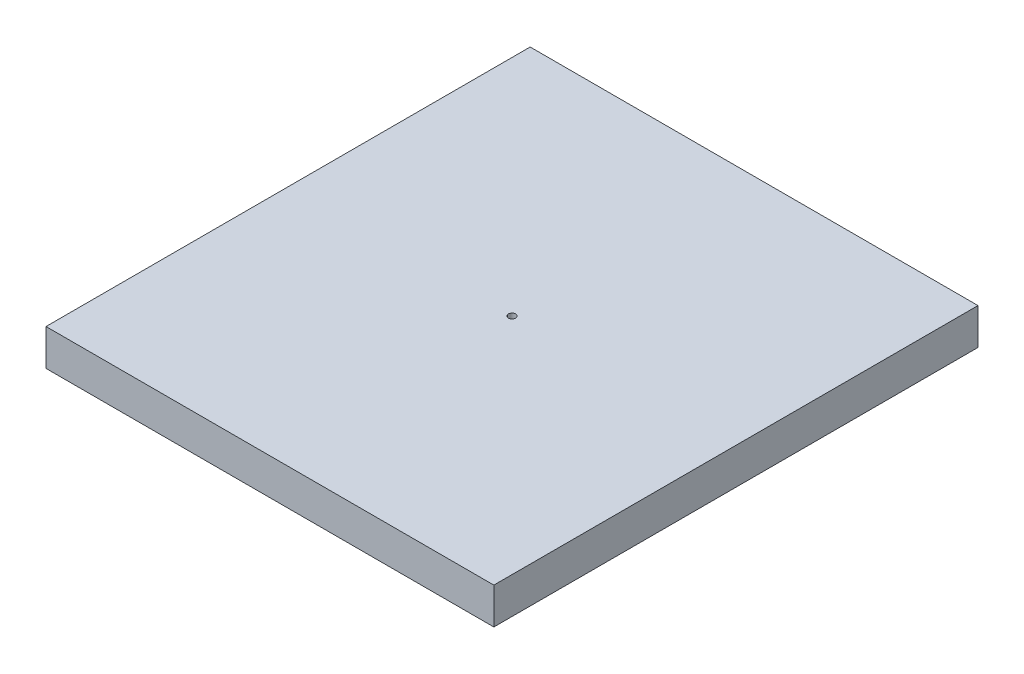
SolidWorks part; units mm, degrees
ref_plane "Front Plane" through (0, 0, 0) normal (0, 0, 1) x (1, 0, 0)
ref_plane "Top Plane" through (0, 0, 0) normal (0, 1, 0) x (1, 0, 0)
ref_plane "Right Plane" through (0, 0, 0) normal (1, 0, 0) x (0, 0, -1)
sketch "Sketch1" plane through (0, 0, 0) normal (0, 1, 0) x (1, 0, 0)
  line L1 (-92.5, -100) -> (92.5, -100)
  line L2 (-92.5, -100) -> (-92.5, 100)
  line L3 (-92.5, 100) -> (92.5, 100)
  line L4 (92.5, -100) -> (92.5, 100)
  line L5 (-92.5, -100) -> (92.5, 100) construction
  line L6 (-92.5, 100) -> (92.5, -100) construction
  point P0 (0, 0)
  dimension "D1" = 185
  dimension "D2" = 200
extrude "Boss-Extrude1" add sketch "Sketch1" along normal mid plane 15
sketch "Sketch2" plane through (0, 7.5, 0) normal (0, 1, 0) x (1, 0, 0)
  circle A0 centre (0, 0) radius 1.5
  dimension "D1" = 3
extrude "Cut-Extrude1" cut sketch "Sketch2" against normal through all
